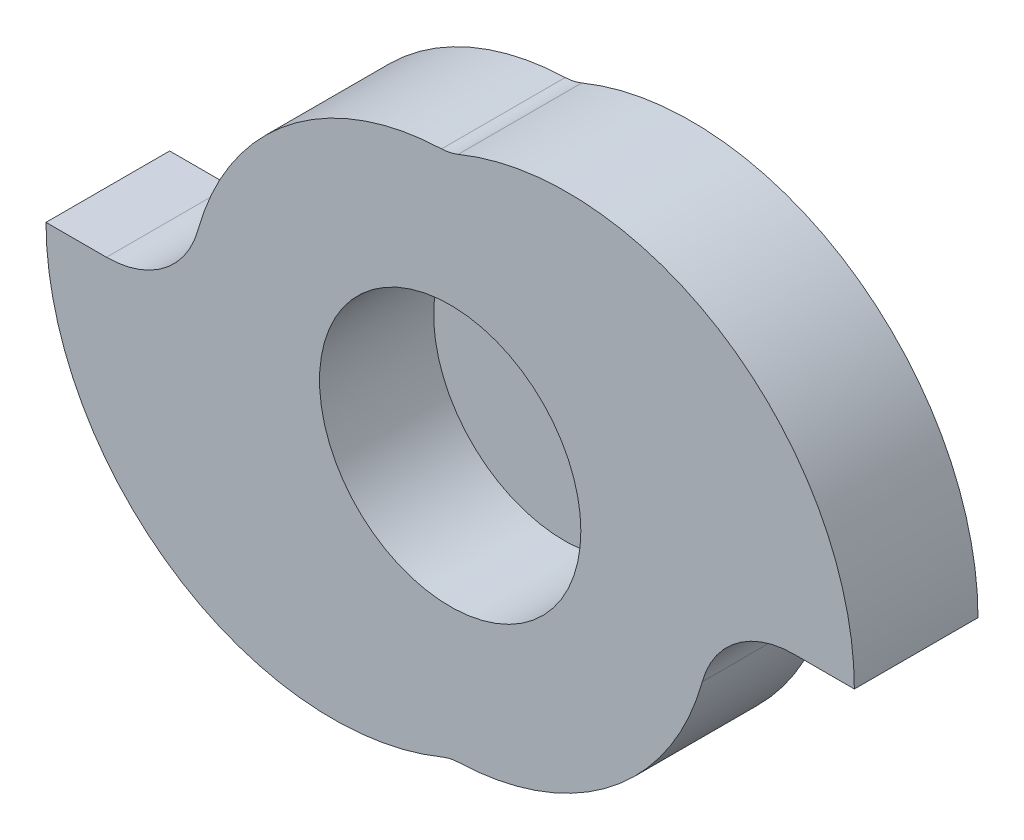
SolidWorks part; units mm, degrees
ref_plane "Front Plane" through (0, 0, 0) normal (0, 0, 1) x (1, 0, 0)
ref_plane "Top Plane" through (0, 0, 0) normal (0, 1, 0) x (1, 0, 0)
ref_plane "Right Plane" through (0, 0, 0) normal (1, 0, 0) x (0, 0, -1)
sketch "Sketch1" plane through (0, 0, 0) normal (0, 0, 1) x (1, 0, 0)
  line L0 (-27.5, 0) -> (-42.5, 0)
  line L1 (27.5, 0) -> (42.5, 0)
  arc A0 (0, 27.5) -> (-27.5, 0) centre (0, 0) ccw
  arc A1 (42.5, 0) -> (0, 27.5) centre (12.3529, 0) ccw
  arc A2 (-42.5, 0) -> (0, -27.5) centre (-12.3529, 0) ccw
  arc A3 (0, -27.5) -> (27.5, 0) centre (0, 0) ccw
  circle A4 centre (0, 0) radius 2.5
  dimension "D1" = 15
  dimension "D3" = 55
  dimension "D2" = 15
extrude "Boss-Extrude1" add sketch "Sketch1" along normal blind 13 contours A3 L1 A1 A0 L0 A2
sketch "Sketch3" plane through (0, 0, 13) normal (0, 0, 1) x (1, 0, 0)
  circle A0 centre (0, 0) radius 13.74
fillet "Fillet1" radius 5 1 edges at (0, 27.5, 6.5)
fillet "Fillet2" radius 10 1 edges at (-27.5, 0, 6.5)
fillet "Fillet3" radius 10 1 edges at (27.5, 0, 6.5)
fillet "Fillet5" radius 5 1 edges at (0, -27.5, 6.5)
extrude "Cut-Extrude2" cut sketch "Sketch3" against normal blind 12 contours A0
sketch "Sketch4" plane through (0, 0, 1) normal (0, 0, 1) x (1, 0, 0)
  line L0 (0, 0) -> (0, 8) construction
  point P3 (2.5496, 6.419)
  line B0 (-2.5981, 6.5) -> (-5.9782, 12.3546)
  line B1 (5.9782, 12.3546) -> (2.5981, 6.5)
  arc B2 (5.9782, 12.3546) -> (-5.9782, 12.3546) centre (0, 0) ccw
  arc B3 (-2.5496, 6.419) -> (2.5496, 6.419) centre (0, 8) ccw
sketch_block_instance "Block-ribs motor-1"
sketch_block "Block-ribs motor"
sketch "Sketch5" plane through (0, 0, 1) normal (0, 0, 1) x (1, 0, 0)
  line L0 (5.9782, 12.3546) -> (2.5981, 6.5) construction
  line L1 (-2.5981, 6.5) -> (-5.9782, 12.3546) construction
  line L2 (5.9782, 12.3546) -> (2.5981, 6.5)
  line L3 (-2.5981, 6.5) -> (-5.9782, 12.3546)
  line L4 (-2.5981, 6.5) -> (-2.5496, 6.419)
  line L5 (2.5496, 6.419) -> (2.5981, 6.5)
  arc A0 (5.9782, 12.3546) -> (-5.9782, 12.3546) centre (0, 0) ccw construction
  arc A1 (-2.5496, 6.419) -> (2.5496, 6.419) centre (0, 8) ccw construction
  arc A2 (5.9782, 12.3546) -> (-5.9782, 12.3546) centre (0, 0) ccw
  arc A3 (-2.5496, 6.419) -> (2.5496, 6.419) centre (0, 8) ccw
sketch "Sketch6" plane through (0, 0, 0) normal (0, 0, -1) x (-1, 0, 0)
  circle A0 centre (0, 0) radius 2.5
extrude "Cut-Extrude3" cut sketch "Sketch6" against normal up to surface (1 mm away) up to face at (13.74, 0, 1)
